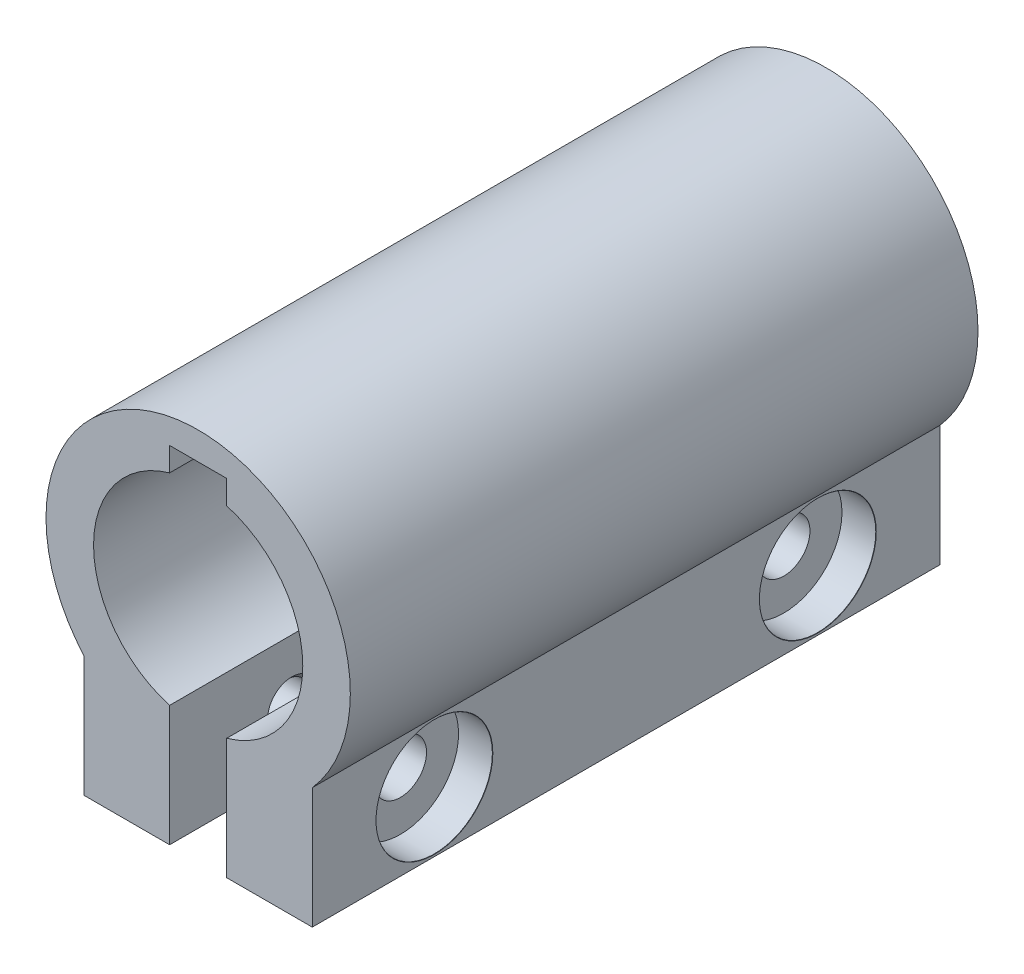
SolidWorks part; units mm, degrees
ref_plane "Front Plane" through (0, 0, 0) normal (0, 0, 1) x (1, 0, 0)
ref_plane "Top Plane" through (0, 0, 0) normal (0, 1, 0) x (1, 0, 0)
ref_plane "Right Plane" through (0, 0, 0) normal (1, 0, 0) x (0, 0, -1)
sketch "Sketch1" plane through (0, 0, 0) normal (0, 0, 1) x (1, 0, 0)
  circle A0 centre (0, 0) radius 11
  circle A1 centre (0, 0) radius 16
  dimension "D1" = 22
  dimension "D2" = 5
extrude "Boss-Extrude1" add sketch "Sketch1" along normal blind 33 and the other way blind 33
sketch "Sketch2" plane through (0, 0, 33) normal (0, 0, 1) x (1, 0, 0)
  line L0 (-3, 10.583) -> (-3, 13.083)
  line L2 (3, 13.083) -> (3, 10.583)
  line L3 (0, 0) -> (0, 13.083) construction
  line L4 (-3, 13.083) -> (0, 13.083)
  line L5 (0, 13.083) -> (3, 13.083)
  line L6 (-3, 10.583) -> (3, 10.583)
  circle A3 centre (0, 0) radius 11 construction
  dimension "D1" = 3
  dimension "D2" = 3
  dimension "D3" = 2.5
  dimension "D4" = 2.5
extrude "Cut-Extrude1" cut sketch "Sketch2" against normal blind 33
mirror "Mirror2" about plane through (0, 0, 0) normal (0, 0, -1) of "Cut-Extrude1"
sketch "Sketch3" plane through (0, 0, 33) normal (0, 0, 1) x (1, 0, 0)
  line L0 (-3, -10.583) -> (-3, -15.7162)
  line L1 (-3, -15.7162) -> (-3, -10.583)
  line L2 (3, -10.583) -> (3, -15.7162)
  line L3 (-3, -10.583) -> (3, -10.583)
  line L4 (-3, -15.7162) -> (-3, -23.283)
  line L5 (-3, -23.283) -> (-12, -23.283)
  line L6 (-12, -23.283) -> (-12, -10.583)
  line L7 (-12, -10.583) -> (-3, -10.583)
  line L8 (3, -15.7162) -> (3, -23.283)
  line L9 (3, -23.283) -> (12, -23.283)
  line L10 (12, -23.283) -> (12, -10.583)
  line L11 (12, -10.583) -> (3, -10.583)
  arc A0 (-3, 10.583) -> (3, 10.583) centre (0, 0) ccw construction
  circle A1 centre (0, 0) radius 16 construction
  circle M6 centre (0, 0) radius 16
  dimension "D1" = 12.7
extrude "Boss-Extrude2" add sketch "Sketch3" against normal through all contours L6 L5 L4 M6 | L9 L10 L8 M6 region at (-7.8946, -18.4352, 33) region at (7.8946, -18.4352, 33)
sketch "Sketch4" plane through (0, 0, 33) normal (0, 0, 1) x (1, 0, 0)
  line L0 (-3, -10.583) -> (-3, -16.2715)
  line L1 (-3, -10.583) -> (3, -10.583)
  line L2 (3, -10.583) -> (3, -15.7162)
  line L3 (-3, -15.7162) -> (-3, -23.283) construction
  line L4 (-3, -16.2715) -> (3, -16.2715)
  line L5 (3, -15.7162) -> (3, -23.283) construction
  line L6 (3, -16.2715) -> (3, -15.7162)
  arc A0 (-3, 10.583) -> (3, 10.583) centre (0, 0) ccw construction
extrude "Cut-Extrude4" cut sketch "Sketch4" against normal through all
sketch "Sketch8" plane through (12, 0, 0) normal (1, 0, 0) x (0, 0, -1)
  line L0 (-33, -16.933) -> (-20.1582, -16.933)
  line L1 (-33, -23.283) -> (-33, -10.583) construction
hole_wizard "CBORE for M5 Hex Head Bolt3" positions "Sketch9" profile "Sketch10" counterbore size "M5" standard "ANSI Metric"
sketch "Sketch9" plane through (12, 0, 0) normal (1, 0, 0) x (0, 0, -1)
  point P0 (-20.1582, -16.933)
  point P4 (0, 0)
sketch "Sketch10" plane through (12, -16.933, 20.1582) normal (0, 1, 0) x (0, 0, -1)
  line L0 (0, 0) -> (0, 11.6524)
  line L1 (0, 11.6524) -> (2.75, 10)
  line L2 (2.75, 10) -> (2.75, 3.58)
  line L3 (2.75, 3.58) -> (6.12, 3.58)
  line L5 (6.12, 3.58) -> (6.12, 0.025)
  line L6 (6.12, 0.025) -> (6.145, 0)
  line L7 (6.145, 0) -> (0, 0)
  line L8 (-6.12, 0.025) -> (-6.145, 0) construction
  line L10 (0, 11.6524) -> (-2.75, 10) construction
  line L11 (0, -6.35) -> (0, 107.95) construction
  dimension "Hole Dia." = 5.5
  dimension "Hole Depth" = 10
  dimension "C'Bore Dia." = 12.24
  dimension "C'Bore Depth" = 3.58
  dimension "Near C'Sink Dia." = 12.29
  dimension "Near C'Sink Angle" = 90
  dimension "Drill Angle" = 118
mirror "Mirror3" about plane through (0, 0, 0) normal (0, 0, 1) of "CBORE for M5 Hex Head Bolt3"
sketch "Sketch12" plane through (-3, 0, 0) normal (1, 0, 0) x (0, 0, -1)
  circle A0 centre (-20.1582, -16.933) radius 3.2234
  circle A1 centre (-20.1582, -16.933) radius 2.75 construction
hole_wizard "M5x0.8 Tapped Hole1" positions "Sketch13" profile "Sketch14" tap size "M5x0.8" standard "ANSI Metric"
sketch "Sketch13" plane through (-3, 0, 0) normal (1, 0, 0) x (0, 0, -1)
  point P0 (-20.1582, -16.933)
sketch "Sketch14" plane through (-3, -16.933, 20.1582) normal (0, 1, 0) x (0, 0, -1)
  line L0 (0, 0) -> (0, 13.6618)
  line L1 (0, 13.6618) -> (2.1, 12.4)
  line L2 (2.1, 12.4) -> (2.1, 0.425)
  line L3 (2.1, 0.425) -> (2.525, 0)
  line L5 (2.525, 0) -> (0, 0)
  line L6 (-2.1, 0.425) -> (-2.525, 0) construction
  line L10 (0, 13.6618) -> (-2.1, 12.4) construction
  line L11 (0, -6.35) -> (0, 107.95) construction
  dimension "Tap Drill Dia." = 4.2
  dimension "Tap Drill Depth" = 12.4
  dimension "Near C'Sink Dia." = 5.05
  dimension "Near C'Sink Angle" = 90
  dimension "Drill Angle" = 118
cosmetic thread "Hole Thread1" parameters "D1"=9, "D2"=5
mirror "Mirror4" about plane through (0, 0, 0) normal (0, 0, 1) of "M5x0.8 Tapped Hole1"
